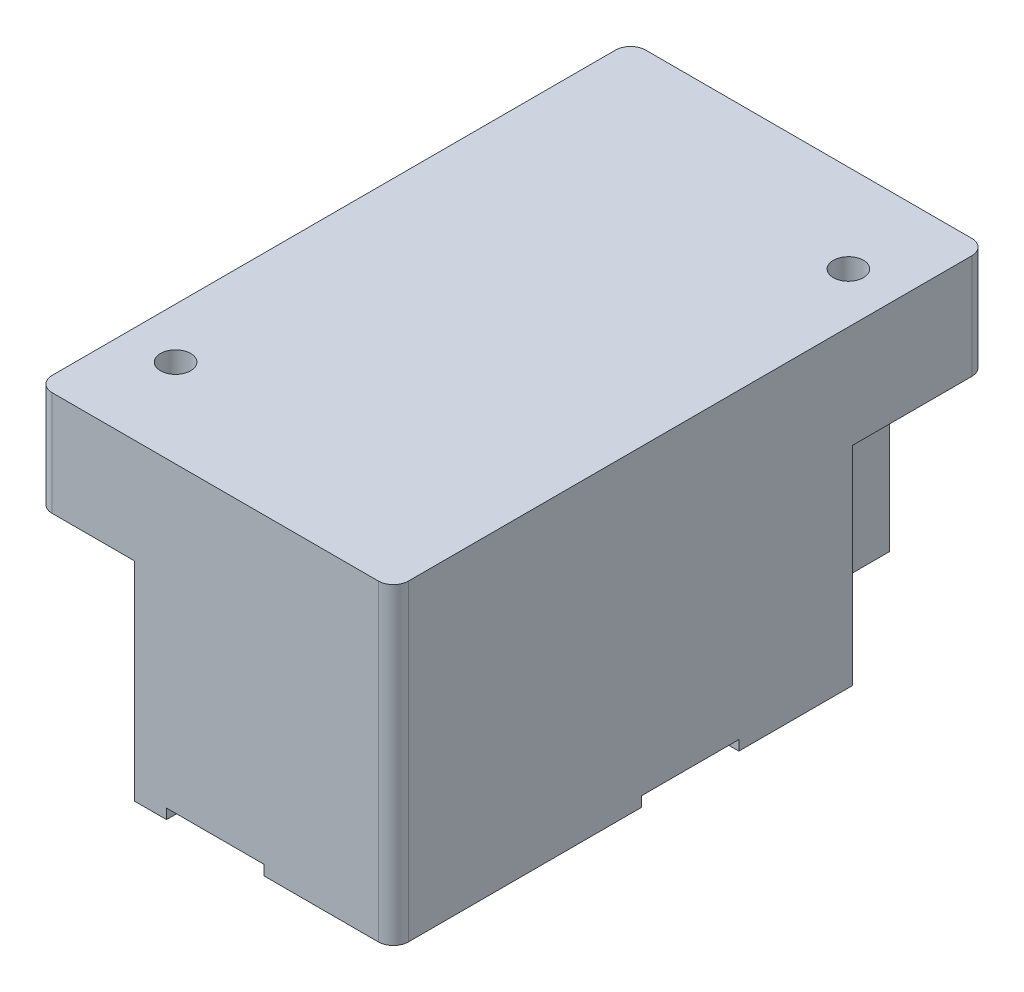
SolidWorks part; units mm, degrees
ref_plane "Front Plane" through (0, 0, 0) normal (0, 0, 1) x (1, 0, 0)
ref_plane "Top Plane" through (0, 0, 0) normal (0, 1, 0) x (1, 0, 0)
ref_plane "Right Plane" through (0, 0, 0) normal (1, 0, 0) x (0, 0, -1)
ref_plane "Plane1" through (0, 0, 0) normal (0, 1, 0) x (1, 0, 0)
sketch "Sketch1" plane through (0, 0, 0) normal (0, 1, 0) x (1, 0, 0)
  line L0 (-9.0043, 14.2367) -> (-9.0043, -14.2367)
  line L1 (-8.2423, -14.9987) -> (8.2423, -14.9987)
  line L2 (9.0043, -14.2367) -> (9.0043, 14.2367)
  line L3 (8.2423, 14.9987) -> (-8.2423, 14.9987)
  arc A0 (-9.0043, -14.2367) -> (-8.2423, -14.9987) centre (-8.2423, -14.2367) ccw
  arc A1 (8.2423, -14.9987) -> (9.0043, -14.2367) centre (8.2423, -14.2367) ccw
  arc A2 (9.0043, 14.2367) -> (8.2423, 14.9987) centre (8.2423, 14.2367) ccw
  arc A3 (-8.2423, 14.9987) -> (-9.0043, 14.2367) centre (-8.2423, 14.2367) ccw
extrude "Boss-Extrude1" add sketch "Sketch1" against normal blind 15.7988
ref_plane "Plane2" through (0, -15.7988, 0) normal (0, 1, 0) x (1, 0, 0)
sketch "Sketch2" plane through (0, -15.7988, 0) normal (0, 1, 0) x (1, 0, 0)
  line L0 (-9.8689, 15.624) -> (-9.8689, -15.3747)
  line L1 (-9.8689, -15.3747) -> (9.8689, -15.3747)
  line L2 (9.8689, -15.3747) -> (9.8689, 15.624)
  line L3 (9.8689, 15.624) -> (-9.8689, 15.624)
  line L4 (-9.0043, 14.9987) -> (-9.0043, -8.2169)
  line L5 (-9.0043, -8.2169) -> (-4.0767, -8.2169)
  line L6 (-4.0767, -8.2169) -> (-4.0767, -14.9987)
  line L7 (-4.0767, -14.9987) -> (9.0043, -14.9987)
  line L8 (9.0043, -14.9987) -> (9.0043, 8.2169)
  line L9 (9.0043, 8.2169) -> (4.0767, 8.2169)
  line L10 (4.0767, 8.2169) -> (4.0767, 14.9987)
  line L11 (4.0767, 14.9987) -> (-9.0043, 14.9987)
extrude "Cut-Extrude1" cut sketch "Sketch2" along normal blind 10.5156
ref_plane "Plane3" through (0, -15.7988, 0) normal (0, 1, 0) x (1, 0, 0)
sketch "Sketch3" plane through (0, -15.7988, 0) normal (0, 1, 0) x (1, 0, 0)
  line L0 (-13.1941, -18.3528) -> (10.5536, -18.3528)
  line L1 (10.5536, -18.3528) -> (10.5536, 18.4536)
  line L2 (10.5536, 18.4536) -> (-13.1941, 18.4536)
  line L3 (-13.1941, 18.4536) -> (-13.1941, -18.3528)
  line L4 (-11.5806, -17.6973) -> (-2.4638, -17.6973)
  line L5 (-2.4638, -17.6973) -> (-2.4638, -6.8834)
  line L6 (-1.7018, -6.1214) -> (1.7018, -6.1214)
  line L7 (2.4638, -6.8834) -> (2.4638, -17.6973)
  line L8 (2.4638, -17.6973) -> (9.2931, -17.6973)
  line L9 (9.2931, -17.6973) -> (9.2931, -2.4638)
  line L10 (9.2931, -2.4638) -> (-2.3114, -2.4638)
  line L11 (-3.0734, -1.7018) -> (-3.0734, 1.7018)
  line L12 (-2.3114, 2.4638) -> (9.2931, 2.4638)
  line L13 (9.2931, 2.4638) -> (9.2931, 17.4956)
  line L14 (9.2931, 17.4956) -> (2.4638, 17.4956)
  line L15 (2.4638, 17.4956) -> (2.4638, 6.8834)
  line L16 (1.7018, 6.1214) -> (-1.7018, 6.1214)
  line L17 (-2.4638, 6.8834) -> (-2.4638, 17.4956)
  line L18 (-2.4638, 17.4956) -> (-11.5806, 17.4956)
  line L19 (-11.5806, 17.4956) -> (-11.5806, -17.6973)
  arc A0 (-2.4638, -6.8834) -> (-1.7018, -6.1214) centre (-1.7018, -6.8834) cw
  arc A1 (1.7018, -6.1214) -> (2.4638, -6.8834) centre (1.7018, -6.8834) cw
  arc A2 (-2.3114, -2.4638) -> (-3.0734, -1.7018) centre (-2.3114, -1.7018) cw
  arc A3 (-3.0734, 1.7018) -> (-2.3114, 2.4638) centre (-2.3114, 1.7018) cw
  arc A4 (2.4638, 6.8834) -> (1.7018, 6.1214) centre (1.7018, 6.8834) cw
  arc A5 (-1.7018, 6.1214) -> (-2.4638, 6.8834) centre (-1.7018, 6.8834) cw
extrude "Cut-Extrude2" cut sketch "Sketch3" along normal blind 0.508
ref_plane "Plane4" through (0, 0, 0) normal (1, 0, 0) x (0, 0, -1)
sketch "Sketch4" plane through (0, 0, 0) normal (1, 0, 0) x (0, 0, -1)
  line L0 (5.1816, -15.7988) -> (3.2004, -15.7988)
  arc A0 (3.2004, -15.7988) -> (5.1816, -15.7988) centre (4.191, -15.2002) ccw
extrude "Boss-Extrude2" add sketch "Sketch4" against normal blind 3.7211 and the other way blind 3.7211
ref_plane "Plane5" through (0, 0, 0) normal (1, 0, 0) x (0, 0, -1)
sketch "Sketch5" plane through (0, 0, 0) normal (1, 0, 0) x (0, 0, -1)
  line L0 (-3.2004, -15.7988) -> (-5.1816, -15.7988)
  arc A0 (-5.1816, -15.7988) -> (-3.2004, -15.7988) centre (-4.191, -15.2002) ccw
extrude "Boss-Extrude3" add sketch "Sketch5" against normal blind 3.7211 and the other way blind 3.7211
ref_plane "Plane6" through (0, 0, 0) normal (0, 0, 1) x (1, 0, 0)
sketch "Sketch6" plane through (0, 0, 0) normal (0, 0, 1) x (1, 0, 0)
  line L0 (-3.7211, -16.1798) -> (-3.7211, -17.0643)
  line L1 (-3.7211, -17.0643) -> (4.0693, -17.0643)
  line L2 (4.0693, -17.0643) -> (4.0693, -16.1798)
  line L3 (4.0693, -16.1798) -> (3.7211, -16.1798)
  line L4 (2.9591, -16.7386) -> (-2.9591, -16.7386)
  arc A0 (3.7211, -16.1798) -> (2.9591, -16.7386) centre (2.9591, -15.9397) cw
  arc A1 (-2.9591, -16.7386) -> (-3.7211, -16.1798) centre (-2.9591, -15.9397) cw
extrude "Cut-Extrude3" cut sketch "Sketch6" against normal blind 6.223 and the other way blind 6.223
ref_plane "Plane7" through (0, -15.7988, 0) normal (0, 1, 0) x (1, 0, 0)
sketch "Sketch7" plane through (0, -15.7988, 0) normal (0, 1, 0) x (1, 0, 0)
  line L0 (-3.9839, 5.4479) -> (-3.9839, -5.4187)
  line L1 (-3.9839, -5.4187) -> (3.9402, -5.4187)
  line L2 (3.9402, -5.4187) -> (3.9402, 5.4479)
  line L3 (3.9402, 5.4479) -> (-3.9839, 5.4479)
  line L4 (-3.2131, 3.2766) -> (3.2131, 3.2766)
  line L5 (3.7211, 3.7846) -> (3.7211, 4.7498)
  line L6 (3.2131, 5.2578) -> (-3.2131, 5.2578)
  line L7 (-3.7211, 4.7498) -> (-3.7211, 3.7846)
  line L8 (-3.2131, -5.2578) -> (3.2131, -5.2578)
  line L9 (3.7211, -4.7498) -> (3.7211, -3.7846)
  line L10 (3.2131, -3.2766) -> (-3.2131, -3.2766)
  line L11 (-3.7211, -3.7846) -> (-3.7211, -4.7498)
  arc A0 (-3.7211, 3.7846) -> (-3.2131, 3.2766) centre (-3.2131, 3.7846) ccw
  arc A1 (3.2131, 3.2766) -> (3.7211, 3.7846) centre (3.2131, 3.7846) ccw
  arc A2 (3.7211, 4.7498) -> (3.2131, 5.2578) centre (3.2131, 4.7498) ccw
  arc A3 (-3.2131, 5.2578) -> (-3.7211, 4.7498) centre (-3.2131, 4.7498) ccw
  arc A4 (-3.7211, -4.7498) -> (-3.2131, -5.2578) centre (-3.2131, -4.7498) ccw
  arc A5 (3.2131, -5.2578) -> (3.7211, -4.7498) centre (3.2131, -4.7498) ccw
  arc A6 (3.7211, -3.7846) -> (3.2131, -3.2766) centre (3.2131, -3.7846) ccw
  arc A7 (-3.2131, -3.2766) -> (-3.7211, -3.7846) centre (-3.2131, -3.7846) ccw
extrude "Cut-Extrude4" cut sketch "Sketch7" against normal blind 0.5588
ref_plane "Plane8" through (0, 0, 0) normal (0, 1, 0) x (1, 0, 0)
sketch "Sketch8" plane through (0, 0, 0) normal (0, 1, 0) x (1, 0, 0)
  circle A0 centre (6.4643, 10.541) radius 0.762
extrude "Cut-Extrude5" cut sketch "Sketch8" against normal blind 5.2832
ref_plane "Plane9" through (0, 0, 0) normal (0, 1, 0) x (1, 0, 0)
sketch "Sketch9" plane through (0, 0, 0) normal (0, 1, 0) x (1, 0, 0)
  circle A0 centre (-6.4643, -10.541) radius 0.762
extrude "Cut-Extrude6" cut sketch "Sketch9" against normal blind 5.2832
sketch "Sketch10" plane through (0, -15.7988, 0) normal (0, -1, 0) x (1, 0, 0)
  text T0 "1"
  text T1 "2"
  text T2 "3"
wrap "Wrap1" sketch "Sketch10" wrap type scribe source sketch "Sketch10" face at (0, -15.7988, -4.2296)
